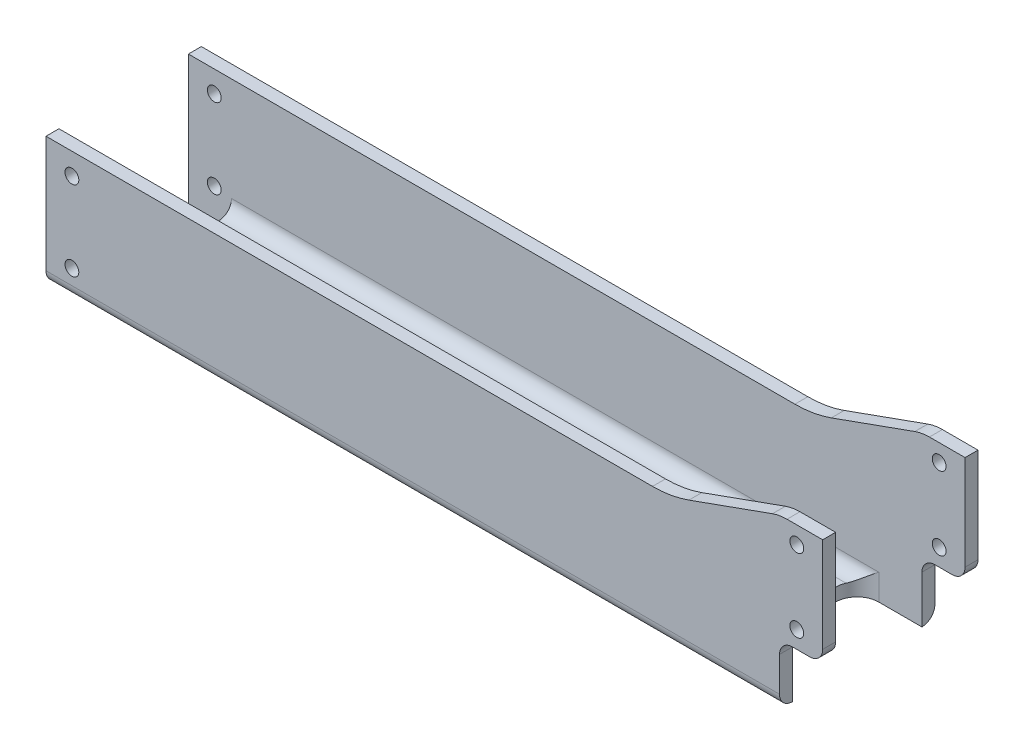
SolidWorks part; units mm, degrees
ref_plane "Front Plane" through (0, 0, 0) normal (0, 0, 1) x (1, 0, 0)
ref_plane "Top Plane" through (0, 0, 0) normal (0, 1, 0) x (1, 0, 0)
ref_plane "Right Plane" through (0, 0, 0) normal (1, 0, 0) x (0, 0, -1)
sketch "Sketch1" plane through (0, 0, 0) normal (0, 0, 1) x (1, 0, 0)
  line L0 (52.7874, 245.1803) -> (193.3525, 245.1803)
  line L4 (52.7874, 245.1803) -> (52.7874, 215.1803)
  line L5 (52.7874, 215.1803) -> (222.7874, 215.1803)
  line L6 (222.7874, 245.1803) -> (222.7874, 215.1803) construction
  line L7 (222.7874, 215.1803) -> (222.7874, 254.1811)
  line L8 (222.7874, 254.1811) -> (201.7956, 246.6492)
  line L9 (241.0832, 254.1811) -> (222.7874, 254.1811) construction
  arc A0 (201.7956, 246.6492) -> (193.3525, 245.1803) centre (193.3525, 270.1803) cw
extrude "Boss-Extrude1" add sketch "Sketch1" against normal blind 3
sketch "Sketch3" plane through (0, 0, -36) normal (0, 0, -1) x (-1, 0, 0)
  line L4 (-222.7874, 254.1811) -> (-222.7874, 215.1803)
  line L5 (-222.7874, 254.1811) -> (-222.7874, 215.1803)
  line L6 (-52.7874, 215.1803) -> (-52.7874, 245.1803)
  line L7 (-52.7874, 245.1803) -> (-193.3525, 245.1803)
  line L9 (-201.7956, 246.6492) -> (-222.7874, 254.1811)
  line L10 (-201.7956, 246.6492) -> (-222.7874, 254.1811)
  line L11 (-222.7874, 215.1803) -> (-52.7874, 215.1803)
  line L12 (-52.7874, 215.1803) -> (-52.7874, 245.1803)
  line L13 (-52.7874, 245.1803) -> (-193.3525, 245.1803)
  line L17 (-222.7874, 215.1803) -> (-52.7874, 215.1803)
  arc A1 (-201.7956, 246.6492) -> (-193.3525, 245.1803) centre (-193.3525, 270.1803) ccw
  arc A2 (-201.7956, 246.6492) -> (-193.3525, 245.1803) centre (-193.3525, 270.1803) ccw
  dimension "D1" = 0
extrude "Boss-Extrude2" add sketch "Sketch3" against normal blind 3 separate body
sketch "Sketch4" plane through (0, 0, -3) normal (0, 0, -1) x (-1, 0, 0)
  line L1 (-52.7874, 215.1803) -> (-207.7874, 215.1803)
  line L2 (-52.7874, 215.1803) -> (-52.7874, 218.1803)
  line L3 (-52.7874, 218.1803) -> (-207.7874, 218.1803)
  line L4 (-207.7874, 215.1803) -> (-207.7874, 218.1803)
extrude "Boss-Extrude3" add sketch "Sketch4" along normal up to surface (30 mm away) up to face at (157.7268, 236.8645, -33)
fillet "Fillet1" radius 5 2 edges at (207.7874, 216.6803, -33) (207.7874, 216.6803, -3)
ref_plane "Plane1" through (130.2874, 0, 0) normal (1, 0, 0) x (0, 0, -1)
fillet "Fillet2" radius 3 4 edges at (132.7874, 218.1803, -3) (132.7874, 218.1803, -33) (137.7874, 215.1803, 0) (137.7874, 215.1803, -36)
sketch "Sketch5" plane through (0, 218.1803, 0) normal (0, 1, 0) x (1, 0, 0)
  line L0 (52.7874, 33) -> (193.3525, 33) construction
  line L1 (52.7874, 3) -> (62.7874, 3)
  line L2 (52.7874, 3) -> (52.7874, 33)
  line L3 (52.7874, 33) -> (62.7874, 33)
  line L4 (62.7874, 3) -> (62.7874, 33)
extrude "Cut-Extrude1" cut sketch "Sketch5" against normal through all both and the other way through all
sketch "Sketch6" plane through (0, 0, 0) normal (0, 0, 1) x (1, 0, 0)
  line L0 (62.7877, 245.1806) -> (62.7877, 215.1806) construction
  line L1 (54.7876, 222.1805) -> (54.7876, 245.1805) construction
  line L2 (62.7877, 245.1806) -> (62.7877, 215.1806) construction
  line L3 (54.7876, 222.1805) -> (54.7876, 245.1805) construction
  line L4 (54.7876, 245.1805) -> (62.7877, 245.1806) construction
  line L5 (58.7876, 245.1805) -> (58.7876, 215.1803) construction
  line L6 (52.7874, 215.1803) -> (62.7874, 215.1803) construction
  circle A0 centre (58.7876, 240.1805) radius 1.6
  circle A1 centre (58.7876, 221.6803) radius 1.6
extrude "Cut-Extrude2" cut sketch "Sketch6" against normal up to surface (36 mm away) up to face at (157.7268, 237.8645, -36)
sketch "Sketch7" plane through (222.7874, 0, 0) normal (1, 0, 0) x (0, 0, -1)
  line L0 (0, 218.1803) -> (0, 254.1811) construction
  line L1 (3, 254.1811) -> (0, 254.1811)
  line L2 (3, 254.1811) -> (3, 229.1811)
  line L3 (3, 229.1811) -> (0, 229.1811)
  line L4 (0, 254.1811) -> (0, 229.1811)
  line L5 (36, 254.1811) -> (36, 218.1803) construction
  line L6 (33, 254.1811) -> (36, 254.1811)
  line L7 (33, 254.1811) -> (33, 229.1811)
  line L8 (33, 229.1811) -> (36, 229.1811)
  line L9 (36, 254.1811) -> (36, 229.1811)
extrude "Boss-Extrude4" add sketch "Sketch7" along normal blind 10
fillet "Fillet3" radius 3 4 edges at (222.7874, 229.1811, -34.5) (222.7874, 229.1811, -1.5) (232.7874, 229.1811, -34.5) (232.7874, 229.1811, -1.5)
sketch "Sketch9" plane through (0, 0, 0) normal (0, 0, 1) x (1, 0, 0)
  line L0 (230.7874, 254.1811) -> (230.7874, 229.3173) construction
  line L1 (230.7874, 254.1811) -> (230.7874, 229.3173) construction
  line L2 (222.7874, 226.1811) -> (222.7874, 254.1811) construction
  line L3 (222.7874, 226.1811) -> (222.7874, 254.1811) construction
  line L4 (222.7874, 254.1811) -> (230.7874, 254.1811) construction
  line L5 (226.7874, 254.1811) -> (226.7874, 229.1811) construction
  circle A0 centre (226.7874, 250.1811) radius 1.6
  circle A1 centre (226.7874, 233.1811) radius 1.6
extrude "Cut-Extrude3" cut sketch "Sketch9" against normal up to surface (36 mm away) up to face at (58.7876, 241.7805, -36)
fillet "Fillet4" radius 10 2 edges at (222.7874, 254.1811, -34.5) (222.7874, 254.1811, -1.5)
